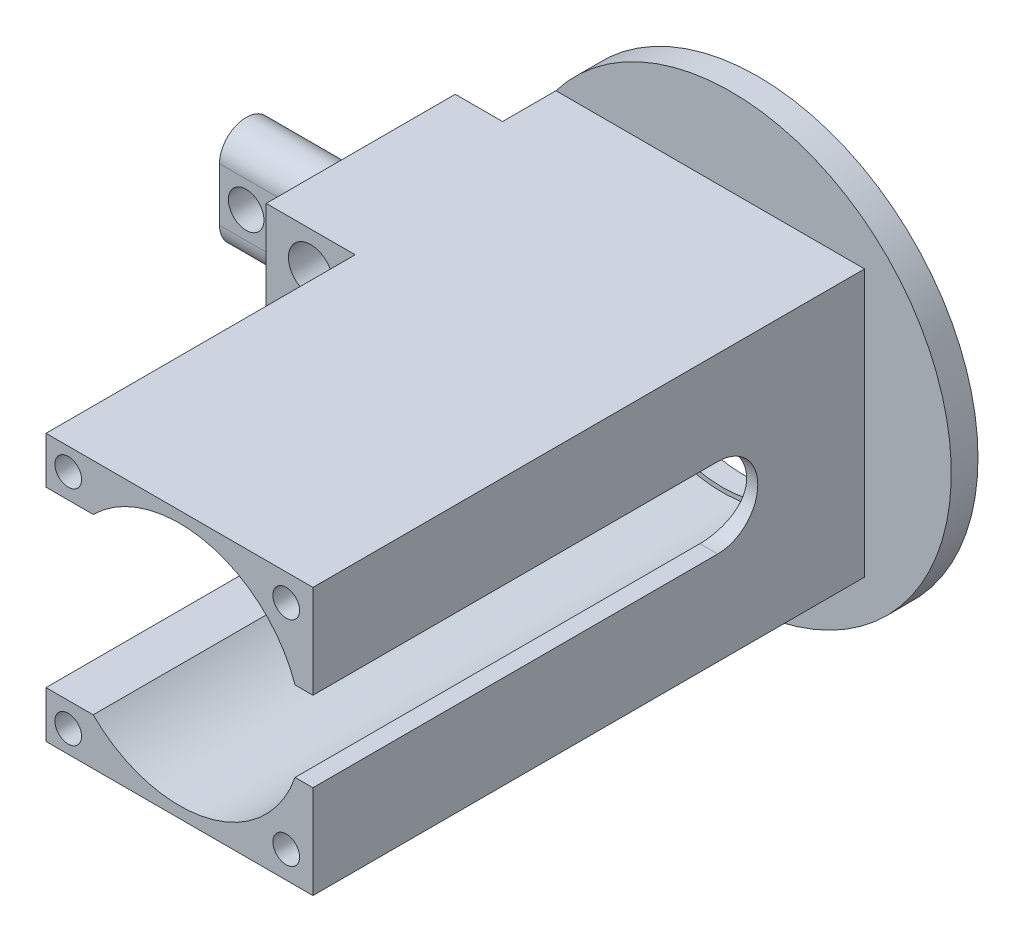
SolidWorks part; units mm, degrees
ref_plane "Ebene vorne" through (0, 0, 0) normal (0, 0, 1) x (1, 0, 0)
ref_plane "Ebene oben" through (0, 0, 0) normal (0, 1, 0) x (1, 0, 0)
ref_plane "Ebene rechts" through (0, 0, 0) normal (1, 0, 0) x (0, 0, -1)
sketch "Sketch1" plane through (0, 0, 0) normal (0, 0, 1) x (1, 0, 0)
  line L1 (-15, 15) -> (15, 15)
  line L2 (-15, 15) -> (-15, -15)
  line L3 (-15, -15) -> (15, -15)
  line L4 (15, 15) -> (15, -15)
  line L5 (0, -15) -> (0, 15) construction
  line L6 (-15, 0) -> (15, 0) construction
  point P0 (0, 0)
  dimension "D1" = 30
  dimension "D2" = 30
extrude "Boss-Extrude1" add sketch "Sketch1" along normal blind 65
sketch "Sketch2" plane through (0, 0, 0) normal (0, 0, -1) x (-1, 0, 0)
  circle A0 centre (0, 0) radius 24.75
  dimension "D1" = 49.5
extrude "Boss-Extrude2" add sketch "Sketch2" against normal blind 3
sketch "Sketch3" plane through (0, 0, 0) normal (0, 0, -1) x (-1, 0, 0)
  circle A0 centre (0, 0) radius 23.75
  circle A1 centre (0, 0) radius 24.75 construction
  dimension "D1" = 1
extrude "Cut-Extrude1" cut sketch "Sketch3" against normal blind 1.6
sketch "Sketch4" plane through (0, 0, 1.6) normal (0, 0, -1) x (-1, 0, 0)
  circle A0 centre (0, 0) radius 13.25
  dimension "D1" = 26.5
extrude "Cut-Extrude4" cut sketch "Sketch4" against normal up to next
sketch "Sketch5" plane through (0, 0, 65) normal (0, 0, 1) x (1, 0, 0)
  circle A0 centre (0, 0) radius 13.75
  dimension "D1" = 27.5
extrude "Cut-Extrude5" cut sketch "Sketch5" against normal blind 61
sketch "Sketch6" plane through (15, 0, 0) normal (1, 0, 0) x (0, 0, -1)
  line L0 (-19.5, 0) -> (-65, 0) construction
  line L1 (-19.5, -4.5) -> (-65, -4.5)
  line L2 (-19.5, 4.5) -> (-65, 4.5)
  line L4 (-3, 15) -> (-3, -15) construction
  line L5 (-65, -15) -> (-65, 15) construction
  arc A0 (-19.5, -4.5) -> (-19.5, 4.5) centre (-19.5, 0) ccw
  arc A1 (-65, 4.5) -> (-65, -4.5) centre (-65, 0) ccw
  point P3 (-42.25, 0)
  dimension "D1" = 4.5
  dimension "D2" = 16.5
  dimension "D3" = 0
extrude "Cut-Extrude9" cut sketch "Sketch6" against normal up to next
sketch "Sketch8" plane through (-15, 0, 0) normal (-1, 0, 0) x (0, 0, 1)
  line L0 (4, -13.75) -> (4, 13.75) construction
  line L1 (19, 10) -> (9, 10)
  line L2 (19, 10) -> (19, -10)
  line L3 (19, -10) -> (9, -10)
  line L4 (9, 10) -> (9, -10)
  line L5 (14, -10) -> (14, 10) construction
  line L6 (19, 0) -> (9, 0) construction
  line L7 (65, -15) -> (3, -15) construction
  point P0 (14, 0)
  dimension "D1" = 5
  dimension "D2" = 20
  dimension "D3" = 10
  dimension "D4" = 5
extrude "Boss-Extrude3" add sketch "Sketch8" along normal blind 10
sketch "Sketch9" plane through (-25, 0, 0) normal (-1, 0, 0) x (0, 0, 1)
  line L0 (14, 3) -> (14, -3) construction
  line L1 (17, 3) -> (17, -3)
  line L2 (11, 3) -> (11, -3)
  line L3 (19, -10) -> (19, 10) construction
  line L4 (19, 10) -> (9, 10) construction
  arc A0 (17, 3) -> (11, 3) centre (14, 3) ccw
  arc A1 (11, -3) -> (17, -3) centre (14, -3) ccw
  point P2 (14, 0)
  dimension "D4" = 3
  dimension "D1" = 6
  dimension "D2" = 5
  dimension "D3" = 10
extrude "Boss-Extrude4" add sketch "Sketch9" along normal blind 18.5
sketch "Sketch10" plane through (0, 0, 17) normal (0, 0, 1) x (1, 0, 0)
  line L0 (-43.5, -3) -> (-43.5, 3) construction
  circle A0 centre (-40.5, 0) radius 2
  circle A1 centre (-32, 0) radius 2
  dimension "D1" = 4
  dimension "D2" = 4
  dimension "D3" = 3
  dimension "D4" = 11.5
extrude "Cut-Extrude10" cut sketch "Sketch10" against normal up to next
sketch "Sketch11" plane through (-15, 0, 0) normal (-1, 0, 0) x (0, 0, 1)
  line L0 (40, 0) -> (65, 0) construction
  line L1 (40, 9.75) -> (65, 9.75)
  line L2 (40, -9.75) -> (65, -9.75)
  line L3 (4, -13.75) -> (4, 13.75) construction
  line L4 (65, 15) -> (65, -15) construction
  arc A0 (40, 9.75) -> (40, -9.75) centre (40, 0) ccw
  arc A1 (65, -9.75) -> (65, 9.75) centre (65, 0) ccw
  point P3 (52.5, 0)
  dimension "D1" = 9.75
  dimension "D2" = 36
  dimension "D3" = 0
extrude "Cut-Extrude11" cut sketch "Sketch11" against normal up to next
sketch "Sketch13" plane through (0, 0, 3) normal (0, 0, 1) x (1, 0, 0)
  line L0 (15, -15) -> (-15, -15) construction
  line L1 (-7.5, -15) -> (7.5, -15)
  line L2 (-7.5, -15) -> (-7.5, -22)
  line L3 (-7.5, -22) -> (7.5, -22)
  line L4 (7.5, -15) -> (7.5, -22)
  line L5 (0, -22) -> (0, -15) construction
  line L6 (-7.5, -18.5) -> (7.5, -18.5) construction
  point P0 (0, -18.5)
  dimension "D1" = 15
  dimension "D2" = 7
  dimension "D3" = 0
  dimension "D4" = 7.5
extrude "Cut-Extrude12" cut sketch "Sketch13" against normal up to next
sketch "Sketch14" plane through (-15, 0, 0) normal (-1, 0, 0) x (0, 0, 1)
  line L0 (19, -10) -> (19, 10) construction
  line L1 (19, 10) -> (30.25, 10)
  line L2 (19, 10) -> (19, -10)
  line L3 (19, -10) -> (30.25, -10)
  line L4 (30.25, 10) -> (30.25, -10)
  line L5 (24.625, -10) -> (24.625, 10) construction
  line L6 (19, 0) -> (30.25, 0) construction
  arc A0 (40, 9.75) -> (40, -9.75) centre (40, 0) ccw construction
  point P0 (24.625, 0)
  point P7 (30.25, 0)
  dimension "D1" = 0
  dimension "D2" = 0
  dimension "D3" = 0
  dimension "D4" = 0
extrude "Boss-Extrude5" add sketch "Sketch14" along normal blind 10
sketch "Sketch15" plane through (-15, 0, 0) normal (-1, 0, 0) x (0, 0, 1)
  line L0 (65, 15) -> (3, 15) construction
  line L1 (9, 15) -> (30.25, 15)
  line L2 (9, 15) -> (9, 10)
  line L3 (9, 10) -> (30.25, 10)
  line L4 (30.25, 15) -> (30.25, 10)
  line L5 (19.625, 10) -> (19.625, 15) construction
  line L6 (9, 12.5) -> (30.25, 12.5) construction
  line L7 (30.25, 10) -> (9, 10) construction
  point P0 (19.625, 12.5)
  dimension "D1" = 0
  dimension "D2" = 0
  dimension "D3" = 0
  dimension "D4" = 0
extrude "Boss-Extrude6" add sketch "Sketch15" along normal blind 10
sketch "Sketch16" plane through (0, -10, 0) normal (0, -1, 0) x (-1, 0, 0)
  line L0 (25, -30.25) -> (15, -30.25) construction
  line L1 (25, -30.25) -> (15, -30.25)
  line L2 (25, -30.25) -> (25, -9)
  line L3 (25, -9) -> (15, -9)
  line L4 (15, -30.25) -> (15, -9)
  line L5 (20, -9) -> (20, -30.25) construction
  line L6 (25, -19.625) -> (15, -19.625) construction
  line L7 (25, -9) -> (25, -30.25) construction
  line L8 (25, -9) -> (15, -9) construction
  line L9 (15, -9) -> (15, -30.25) construction
  point P0 (20, -19.625)
  dimension "D1" = 0
  dimension "D2" = 0
  dimension "D3" = 0
  dimension "D4" = 0
extrude "Boss-Extrude7" add sketch "Sketch16" along normal blind 5
sketch "Sketch18" plane through (0, 0, 30.25) normal (0, 0, 1) x (1, 0, 0)
  line L0 (-15, -15) -> (-25, -15) construction
  line L1 (-25, 15) -> (-15, 15) construction
  line L2 (-25, -15) -> (-25, 15) construction
  circle A0 centre (-20, -11) radius 2.5
  circle A1 centre (-20, 11) radius 2.5
  dimension "D2" = 5
  dimension "D3" = 5
  dimension "D1" = 0
  dimension "D4" = 4
  dimension "D5" = 4
  dimension "D6" = 5
extrude "Cut-Extrude13" cut sketch "Sketch18" against normal blind 5.5
sketch "Sketch19" plane through (0, 0, 65) normal (0, 0, 1) x (1, 0, 0)
  line L0 (15, 15) -> (-15, 15) construction
  line L1 (-15, -15) -> (15, -15) construction
  line L2 (15, -15) -> (15, -4.5) construction
  line L3 (15, 4.5) -> (15, 15) construction
  line L4 (-15, 15) -> (-15, 9.75) construction
  line L5 (-15, -9.75) -> (-15, -15) construction
  circle A0 centre (12, -12) radius 1.5
  circle A1 centre (12, 12) radius 1.5
  circle A2 centre (-12.5, -12.5) radius 1.5
  circle A3 centre (-12.5, 12.5) radius 1.5
  dimension "D1" = 3
  dimension "D2" = 3
  dimension "D7" = 3
  dimension "D8" = 3
  dimension "D3" = 3
  dimension "D4" = 3
  dimension "D5" = 3
  dimension "D6" = 3
  dimension "D9" = 2.5
  dimension "D10" = 2.5
  dimension "D11" = 2.5
  dimension "D12" = 2.5
extrude "Cut-Extrude14" cut sketch "Sketch19" against normal blind 3.5
sketch "Sketch20" plane through (-25, 0, 0) normal (-1, 0, 0) x (0, 0, 1)
  line L0 (30.25, -15) -> (9, -15) construction
  line L1 (30.25, 15) -> (9, 15) construction
  line L2 (9, 15) -> (9, -15) construction
  circle A0 centre (14, 11) radius 1.5
  circle A1 centre (14, -11) radius 1.5
  dimension "D2" = 3
  dimension "D3" = 3
  dimension "D1" = 0
  dimension "D4" = 4
  dimension "D5" = 4
  dimension "D6" = 5
extrude "Cut-Extrude15" cut sketch "Sketch20" against normal blind 3.5
sketch "Sketch21" plane through (0, 0, 9) normal (0, 0, -1) x (-1, 0, 0)
  line L1 (25, 15) -> (15, 15) construction
  line L6 (15, 15) -> (15, -15)
  line L7 (15, -15) -> (25, -15)
  line L8 (25, -15) -> (25, 15)
  line L9 (25, 15) -> (15, 15)
  line L10 (15, 15) -> (15, -15)
  line L11 (15, -15) -> (19.6866, -15)
  line L13 (19.6866, 15) -> (15, 15)
  arc A0 (19.6866, -15) -> (19.6866, 15) centre (0, 0) ccw
  dimension "D1" = 24.75
  dimension "D3" = 0
  dimension "D4" = 0
extrude "Boss-Extrude8" add sketch "Sketch21" along normal up to surface (6 mm away) up to face at (-24.75, 0, 3)
